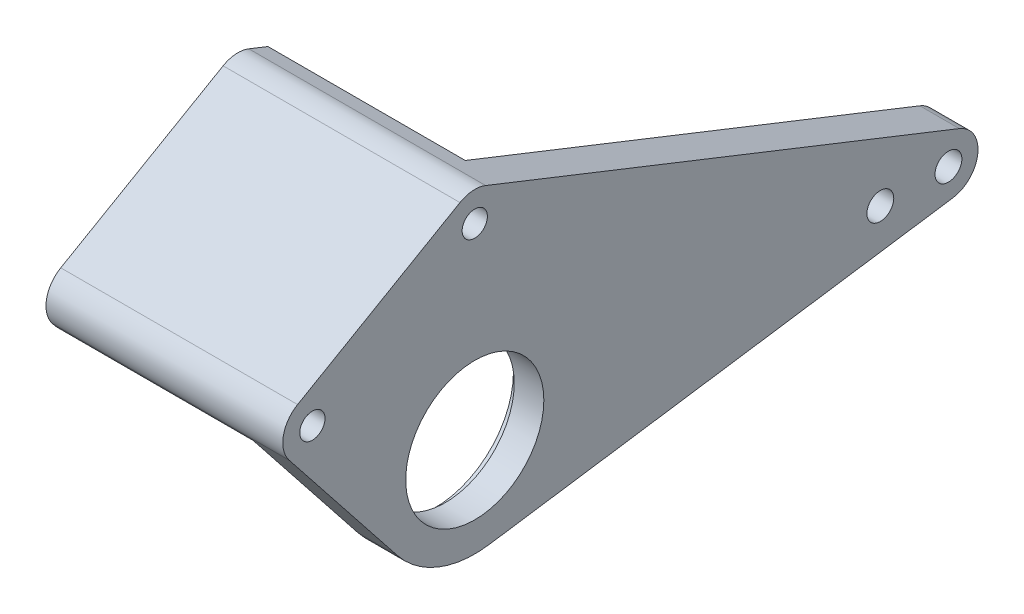
SolidWorks part; units mm, degrees
ref_plane "Front Plane" through (0, 0, 0) normal (0, 0, 1) x (1, 0, 0)
ref_plane "Top Plane" through (0, 0, 0) normal (0, 1, 0) x (1, 0, 0)
ref_plane "Right Plane" through (0, 0, 0) normal (1, 0, 0) x (0, 0, -1)
sketch "Sketch1" plane through (0, 0, 0) normal (1, 0, 0) x (0, 0, -1)
  line L0 (1.7528, 4.4282) -> (-74.4472, 34.5907)
  line L1 (-78.5812, 34.2869) -> (-104.7027, 19.2057)
  line L2 (-106.0548, 12.1242) -> (-88.6443, -9.8568)
  line L3 (-73.8849, -15.7053) -> (0.6945, -4.7116)
  line L4 (-102.3215, 15.0813) -> (-76.2, 0) construction
  line L5 (-76.2, 0) -> (-76.2, 30.1625) construction
  line L6 (0, 0) -> (-76.2, 0) construction
  circle A0 centre (0, 0) radius 2.159
  arc A1 (0.6945, -4.7116) -> (1.7528, 4.4282) centre (0, 0) ccw
  arc A2 (-74.4472, 34.5907) -> (-78.5812, 34.2869) centre (-76.2, 30.1625) ccw
  arc A3 (-104.7027, 19.2057) -> (-106.0548, 12.1242) centre (-102.3215, 15.0813) ccw
  arc A4 (-88.6443, -9.8568) -> (-73.8849, -15.7053) centre (-76.2, 0) ccw
  circle A5 centre (-76.2, 0) radius 11.1125
  circle A6 centre (-76.2, 30.1625) radius 2.032
  circle A7 centre (-76.2, 0) radius 26.1938 construction
  circle A8 centre (-102.3215, 15.0813) radius 2.032
  circle A9 centre (-10.955, 0) radius 2.159
  dimension "D1" = 4.318
  dimension "D2" = 9.525
  dimension "D3" = 22.225
  dimension "D4" = 4.7625
  dimension "D5" = 15.875
  dimension "D6" = 52.3875
  dimension "D10" = 4.064
  dimension "D7" = 30.1625
  dimension "D8" = 76.2
  dimension "D9" = 60
  dimension "D11" = 10.955
extrude "Boss-Extrude1" add sketch "Sketch1" along normal blind 6.35
sketch "Sketch2" plane through (6.35, 0, 0) normal (1, 0, 0) x (0, 0, -1)
  circle A0 centre (-76.2, 0) radius 12.573
  dimension "D1" = 25.146
extrude "Cut-Extrude1" cut sketch "Sketch2" against normal blind 1.5875
sketch "Sketch3" plane through (6.35, 0, 0) normal (1, 0, 0) x (0, 0, -1)
  line L0 (-74.4472, 34.5907) -> (-71.374, 33.3742)
  line L1 (-76.2, 33.902) -> (-79.4385, 32.0322)
  line L2 (-79.4385, 32.0322) -> (-79.4385, 28.2928)
  line L3 (-79.4385, 28.2928) -> (-76.2, 26.423)
  line L4 (-76.2, 26.423) -> (-72.9615, 28.2928)
  line L5 (-72.9615, 28.2928) -> (-72.9615, 32.0322)
  line L6 (-72.9615, 32.0322) -> (-76.2, 33.902)
  line L7 (-102.3215, 18.8207) -> (-105.56, 16.951)
  line L8 (-105.56, 16.951) -> (-105.56, 13.2115)
  line L9 (-105.56, 13.2115) -> (-102.3215, 11.3418)
  line L10 (-102.3215, 11.3418) -> (-99.083, 13.2115)
  line L11 (-99.083, 13.2115) -> (-99.083, 16.951)
  line L12 (-99.083, 16.951) -> (-102.3215, 18.8207)
  line L13 (-78.5813, 34.2869) -> (-104.7027, 19.2057)
  line L14 (-106.0548, 12.1242) -> (-102.1951, 7.2513)
  line L17 (1.7528, 4.4282) -> (-74.4472, 34.5907) construction
  line L18 (-71.374, 26.5525) -> (-71.374, 33.3742)
  line L20 (-78.5812, 34.2869) -> (-104.7027, 19.2057) construction
  line L21 (-106.0548, 12.1242) -> (-88.6443, -9.8568) construction
  circle A0 centre (-76.2, 30.1625) radius 3.2385 construction
  circle A1 centre (-102.3215, 15.0813) radius 3.2385 construction
  arc A4 (-74.4472, 34.5907) -> (-78.5813, 34.2869) centre (-76.2, 30.1625) ccw
  arc A5 (-104.7027, 19.2057) -> (-106.0548, 12.1242) centre (-102.3215, 15.0813) ccw
  arc A6 (-102.1951, 7.2513) -> (-71.374, 26.5525) centre (-76.2, 0) cw
  arc A7 (-74.4472, 34.5907) -> (-78.5812, 34.2869) centre (-76.2, 30.1625) ccw construction
  arc A8 (-104.7027, 19.2057) -> (-106.0548, 12.1242) centre (-102.3215, 15.0813) ccw construction
  line M18 (1.7528, 4.4282) -> (-74.4472, 34.5907)
  arc M19 (-74.4472, 34.5907) -> (-78.5812, 34.2869) centre (-76.2, 30.1625) ccw
  line M20 (-78.5812, 34.2869) -> (-104.7027, 19.2057)
  arc M21 (-104.7027, 19.2057) -> (-106.0548, 12.1242) centre (-102.3215, 15.0813) ccw
  line M22 (-106.0548, 12.1242) -> (-88.6443, -9.8568)
  dimension "D4" = 26.9875
  dimension "D1" = 6.477
  dimension "D2" = 6.477
  dimension "D3" = 1.5875
extrude "Boss-Extrude2" add sketch "Sketch3" along normal blind 31.75 contours A6 L10 L9 L8 L7 L12 L11 L3 L2 L1 L6 L5 L4 L18 M22 M18 M19 M20 M21 region at (6.35, 23.916, 90.2574)
fillet "Fillet1" radius 3.175 2 edges at (22.225, 26.5525, 71.374) (22.225, 7.2513, 102.1951)
mirror "Mirror1" about plane through (6.35, 0, 0) normal (1, 0, 0) of bodies 104 102
delete or keep bodies "Body-Delete/Keep 1" type delete bodies bodies 104
